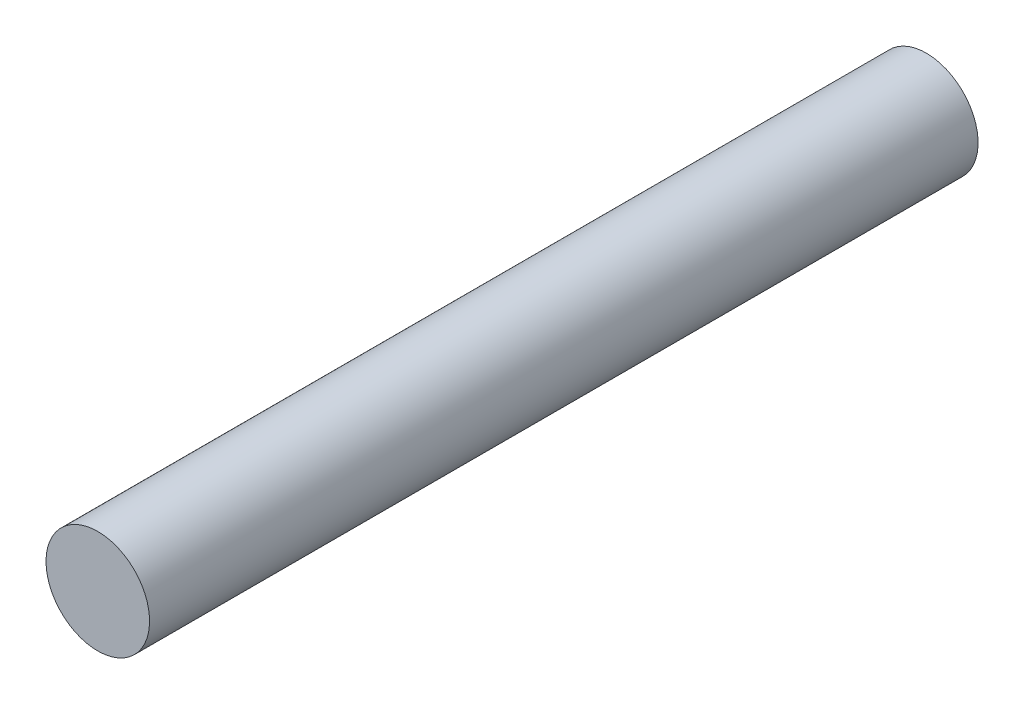
SolidWorks part; units mm, degrees
ref_plane "Front Plane" through (0, 0, 0) normal (0, 0, 1) x (1, 0, 0)
ref_plane "Top Plane" through (0, 0, 0) normal (0, 1, 0) x (1, 0, 0)
ref_plane "Right Plane" through (0, 0, 0) normal (1, 0, 0) x (0, 0, -1)
sketch "Sketch1" plane through (0, 0, 0) normal (0, 0, 1) x (1, 0, 0)
  circle A0 centre (0, 0) radius 4.7625
  dimension "D1" = 9.525
extrude "Boss-Extrude1" add sketch "Sketch1" along normal blind 76.2
